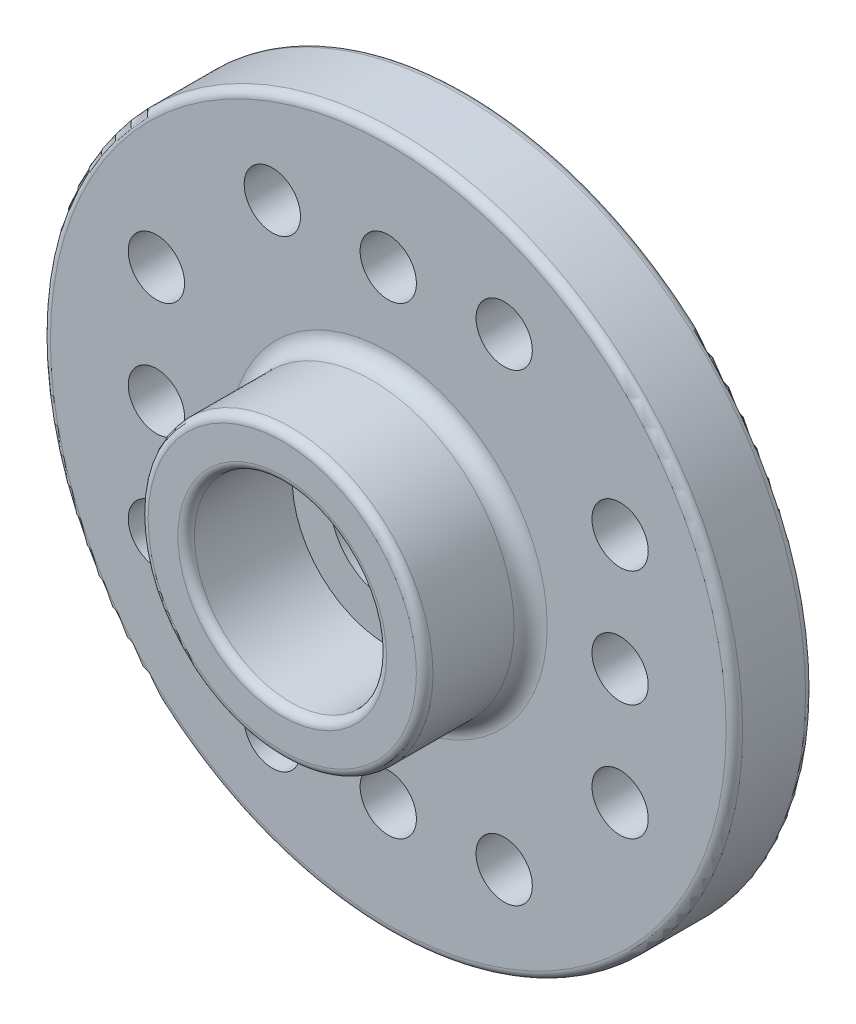
SolidWorks part; units mm, degrees
ref_plane "Front Plane" through (0, 0, 0) normal (0, 0, 1) x (1, 0, 0)
ref_plane "Top Plane" through (0, 0, 0) normal (0, 1, 0) x (1, 0, 0)
ref_plane "Right Plane" through (0, 0, 0) normal (1, 0, 0) x (0, 0, -1)
sketch "Sketch1" plane through (0, 0, 0) normal (0, 0, 1) x (1, 0, 0)
  circle A0 centre (0, 0) radius 10.45
  circle A1 centre (0, 0) radius 1.75
  dimension "D1" = 20.9
  dimension "D2" = 3.5
extrude "Boss-Extrude1" add sketch "Sketch1" along normal blind 2.4
sketch "Sketch2" plane through (0, 0, 2.4) normal (0, 0, 1) x (1, 0, 0)
  circle A0 centre (0, 0) radius 4.3
  circle A1 centre (0, 0) radius 2.9
  dimension "D1" = 8.6
  dimension "D2" = 5.8
extrude "Boss-Extrude2" add sketch "Sketch2" along normal blind 3.2
sketch "Sketch4" plane through (0, 0, 0) normal (0, 0, -1) x (-1, 0, 0)
  circle A0 centre (0, 0) radius 3.3
  circle A1 centre (0, 0) radius 3.6
  dimension "D1" = 7.2
  dimension "D2" = 6.6
extrude "Boss-Extrude3" add sketch "Sketch4" along normal blind 0.2
sketch "Sketch5" plane through (0, 0, 0) normal (0, 0, -1) x (-1, 0, 0)
  circle A0 centre (0, 0) radius 3.3 construction
  circle A1 centre (0, 0) radius 3.3
  circle A2 centre (0, 0) radius 4
  circle A3 centre (0, 0) radius 3.6 construction
  circle A4 centre (0, 0) radius 3.6
  circle M2 centre (0, 0) radius 3.6
  dimension "D1" = 8
extrude "Cut-Extrude2" cut sketch "Sketch5" against normal blind 0.4 contours A1 | A2 M2 region at (0, 0, 0) region at (3.8869, 0, 0)
sketch "Sketch6" plane through (0, 0, 0) normal (0, 0, -1) x (-1, 0, 0)
  line L0 (0, 0) -> (0, 7) construction
  circle A0 centre (0, 7) radius 0.85
  circle A1 centre (3.5, 7) radius 0.85
  circle A2 centre (-3.5, 7) radius 0.85
  dimension "D1" = 1.7
  dimension "D2" = 3.5
  dimension "D3" = 3.5
  dimension "D4" = 7
extrude "Cut-Extrude3" cut sketch "Sketch6" against normal through all contours A0 | A1 | A2 region at (0, 7, 0) region at (-3.5, 7, 0)
pattern_circular "CirPattern1" count 4 over 360 about axis through (0, 0, 2.4) along (0, 0, -1) of "Cut-Extrude3"
fillet "Fillet1" radius 0.25 4 edges at (4.3, 0, 5.6) (10.45, 0, 2.4) (10.45, 0, 0) (2.9, 0, 5.6)
fillet "Fillet2" radius 0.5 1 edges at (4.3, 0, 2.4)
